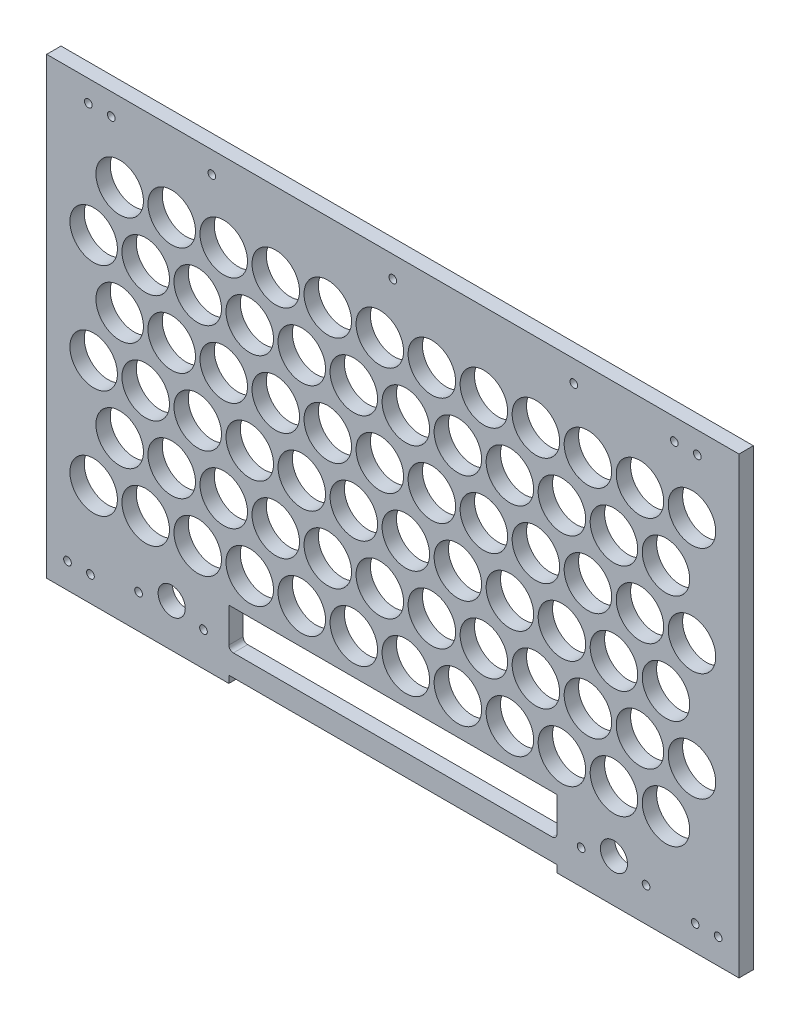
SolidWorks part; units mm, degrees
material "ABS"
ref_plane "X-Y Datum" through (0, 0, 0) normal (0, 0, 1) x (1, 0, 0)
ref_plane "X-Z Datum" through (0, 0, 0) normal (0, 1, 0) x (1, 0, 0)
ref_plane "Y-Z Datum" through (0, 0, 0) normal (1, 0, 0) x (0, 0, -1)
sketch "Sketch1" plane through (0, 0, 0) normal (0, 0, 1) x (1, 0, 0)
  line L1 (-143.025, 70.775) -> (143.025, 70.775)
  line L2 (-143.025, 70.775) -> (-143.025, -70.775)
  line L3 (-143.025, -70.775) -> (143.025, -70.775)
  line L4 (143.025, 70.775) -> (143.025, -70.775)
  line L5 (-143.025, 70.775) -> (143.025, -70.775) construction
  line L6 (-143.025, -70.775) -> (143.025, 70.775) construction
  line L13 (-153.025, -105.775) -> (153.025, -105.775)
  line L14 (-153.025, 91.65) -> (153.025, 91.65)
  line L15 (-153.025, 91.65) -> (-153.025, -105.775)
  line L16 (153.025, 91.65) -> (153.025, -105.775)
  line L17 (153.025, 70.775) -> (153.025, -70.775) construction
  line L18 (-143.025, 91.65) -> (143.025, 91.65) construction
  line L19 (-143.025, -105.775) -> (143.025, -105.775) construction
  line L20 (-153.025, 70.775) -> (-153.025, -70.775) construction
  line L21 (-132.25, -60) -> (-109.25, -60) construction
  circle A0 centre (-132.25, -60) radius 10.775
  circle A1 centre (-109.25, -60) radius 10.775 construction
  circle A2 centre (-120.75, -36) radius 10.775
  point P0 (0, 0)
  point P16 (-120.75, -60)
  dimension "D1" = 21.55
  dimension "D2" = 23
  dimension "D3" = 24
  dimension "D5" = 141.55
  dimension "D6" = 286.05
  dimension "D7" = 35
  dimension "D8" = 20.875
  dimension "D9" = 10
  dimension "D10" = 10
extrude "Boss-Extrude1" add sketch "Sketch1" along normal blind 6.35 contours A0 L3 L4 L1 L2 A2 | A2 | A0 | A0 L2 L3 | L1 L4 L3 L2 region at (2.4105, 0.9241, 0) region at (-140.6182, -68.3682, 0) region at (-132.25, -60, 0) region at (-149.383, -7.0625, 0) region at (-120.75, -36, 0)
sketch "Sketch3" plane through (0, 0, 6.35) normal (0, 0, 1) x (1, 0, 0)
  line L4 (143.025, 70.775) -> (-143.025, 70.775)
  line L5 (143.025, -70.775) -> (143.025, 70.775)
  line L6 (-143.025, -70.775) -> (143.025, -70.775)
  line L7 (-143.025, 70.775) -> (-143.025, -70.775)
  line L8 (143.025, 70.775) -> (-143.025, 70.775)
  line L9 (143.025, -70.775) -> (143.025, 70.775)
  line L10 (-143.025, -70.775) -> (143.025, -70.775)
  line L11 (-143.025, 70.775) -> (-143.025, -70.775)
  circle A0 centre (-132.25, -60) radius 10.4988
  circle A1 centre (-120.75, -36) radius 10.775
  circle A2 centre (-120.75, -36) radius 10.775 construction
  circle A3 centre (-132.25, -60) radius 10.775
  circle A4 centre (-132.25, -60) radius 10.775 construction
  circle A5 centre (-120.75, -36) radius 10.4988
  dimension "D4" = 20.9976
  dimension "D1" = 0
  dimension "D2" = 0
  dimension "D3" = 0
extrude "Cut-Extrude1" cut sketch "Sketch3" against normal through all contours A4 | A0 region at (-132.25, -60, 6.35)
sketch "Sketch4" plane through (0, 0, 6.35) normal (0, 0, 1) x (1, 0, 0)
  line L4 (143.025, 70.775) -> (-143.025, 70.775)
  line L5 (143.025, -70.775) -> (143.025, 70.775)
  line L6 (-143.025, -70.775) -> (143.025, -70.775)
  line L7 (-143.025, 70.775) -> (-143.025, -70.775)
  line L8 (143.025, 70.775) -> (-143.025, 70.775)
  line L9 (143.025, -70.775) -> (143.025, 70.775)
  line L10 (-143.025, -70.775) -> (143.025, -70.775)
  line L11 (-143.025, 70.775) -> (-143.025, -70.775)
  line L12 (143.025, 70.775) -> (-143.025, 70.775)
  line L13 (-143.025, 70.775) -> (-143.025, -70.775)
  line L14 (-143.025, -70.775) -> (143.025, -70.775)
  line L15 (143.025, -70.775) -> (143.025, 70.775)
  line L16 (143.025, 70.775) -> (-143.025, 70.775)
  line L17 (-143.025, 70.775) -> (-143.025, -70.775)
  line L18 (-143.025, -70.775) -> (143.025, -70.775)
  line L19 (143.025, -70.775) -> (143.025, 70.775)
  circle A1 centre (-120.75, -36) radius 10.4988
  circle A3 centre (-120.75, -36) radius 10.4988
  circle A5 centre (-132.25, -60) radius 10.4988
  circle A6 centre (-132.25, -60) radius 10.4988
  dimension "D4" = 0
  dimension "D1" = 0
  dimension "D2" = 0
  dimension "D3" = 0
extrude "Cut-Extrude2" cut sketch "Sketch4" against normal through all contours A3 region at (-120.75, -36, 6.35)
pattern_linear "LPattern1" count 12 spacing 23 along (1, 0, 0) of "Cut-Extrude1", "Cut-Extrude2"
pattern_linear "LPattern2" count 3 spacing 48 along (0, 1, 0) of "LPattern1"
sketch "Sketch5" plane through (0, 0, 0) normal (0, 0, -1) x (-1, 0, 0)
sketch "Sketch13" plane through (0, 91.65, 0) normal (0, 1, 0) x (1, 0, 0)
  line L4 (153.025, 0) -> (-153.025, 0)
  line L5 (-153.025, 0) -> (-153.025, -6.35)
  line L6 (-153.025, -6.35) -> (153.025, -6.35)
  line L7 (153.025, -6.35) -> (153.025, 0)
  line L8 (153.025, 0) -> (-153.025, 0)
  line L9 (-153.025, 0) -> (-153.025, -6.35)
  line L10 (-153.025, -6.35) -> (153.025, -6.35)
  line L11 (153.025, -6.35) -> (153.025, 0)
  dimension "D1" = 0
extrude "Boss-Extrude2" add sketch "Sketch13" along normal blind 3.175
sketch "Sketch14" plane through (0, 0, 0) normal (0, 0, -1) x (-1, 0, 0)
  circle A0 centre (-97.75, -86.775) radius 6
extrude "Cut-Extrude3" cut sketch "Sketch14" against normal through all
mirror "Mirror1" about plane through (0, 0, 0) normal (1, 0, 0) of "Cut-Extrude3"
sketch "Sketch15" plane through (0, 0, 0) normal (0, 0, -1) x (-1, 0, 0)
  point P0 (-111.94, -90.775)
  point P1 (-83.25, -90.775)
  point P3 (83.712, -90.775)
  point P11 (80, 85.3)
  point P13 (0, 85.3)
  point P15 (-80, 85.3)
  point P41 (112.402, -90.775)
  point P47 (-143.8175, -94.6)
  point P50 (-133.6575, -94.6)
  point P54 (-134.61, 85.3)
  point P57 (-124.45, 85.3)
  point P61 (124.45, 85.3)
  point P64 (134.61, 85.3)
  point P68 (133.6575, -94.6)
  point P71 (143.8175, -94.6)
hole_wizard "M3 Clearance Hole1" positions "Sketch15" profile "Sketch16" hole size "M3" standard "ANSI Metric" end condition through all
sketch "Sketch16" plane through (111.94, -90.775, 0) normal (1, 0, 0) x (0, 1, 0)
  line L0 (0, 0) -> (0, 6.35)
  line L1 (0, 6.35) -> (1.7, 6.35)
  line L2 (1.7, 6.35) -> (1.7, 0)
  line L5 (1.7, 0) -> (0, 0)
  line L11 (0, -6.35) -> (0, 107.95) construction
  dimension "Thru Hole Dia." = 3.4
  dimension "Thru Hole Depth" = 6.35
sketch "Sketch17" plane through (0, 0, 0) normal (0, 0, -1) x (-1, 0, 0)
  line L0 (0, -105.775) -> (0, -77.9164) construction
  line L1 (153.025, -105.775) -> (-153.025, -105.775) construction
  circle A0 centre (0, -90.775) radius 2.25
  circle A1 centre (140.5494, 12) radius 2.25
  circle A2 centre (-140.6875, -12) radius 2.25
  point P0 (-140.6875, -12)
  point P1 (140.5494, 12)
  point P9 (0, -90.775)
  point P11 (83.712, -90.775)
  dimension "D1" = 4.5
extrude "Cut-Extrude4" [suppressed] cut sketch "Sketch17" against normal through all
sketch "Sketch18" plane through (0, -105.775, 0) normal (0, -1, 0) x (1, 0, 0)
  line L0 (0, 0) -> (0, 6.35)
  line L1 (-153.025, 0) -> (153.025, 0) construction
  line L2 (-153.025, 6.35) -> (153.025, 6.35) construction
  line L4 (-72.5, 6.35) -> (72.5, 6.35)
  line L5 (-72.5, 6.35) -> (-72.5, 0)
  line L6 (-72.5, 0) -> (72.5, 0)
  line L7 (72.5, 6.35) -> (72.5, 0)
  line L8 (-72.5, 6.35) -> (72.5, 0) construction
  line L9 (-72.5, 0) -> (72.5, 6.35) construction
  point P6 (0, 3.175)
  line M3 (-153.025, 0) -> (153.025, 0)
  line M5 (153.025, 6.35) -> (-153.025, 6.35)
  dimension "D1" = 145
extrude "Cut-Extrude5" cut sketch "Sketch18" against normal blind 30 contours L7 L0 M5 M3 | L5 L0 M5 M3 region at (-36.25, -105.775, 3.175) region at (36.25, -105.775, 3.175)
fillet "Fillet1" [suppressed] radius 8
sketch "Sketch19" plane through (0, 0, 0) normal (0, 0, -1) x (-1, 0, 0)
  line L0 (-72.5, -75.775) -> (-72.5, -105.775) construction
  line L1 (-72.5, -102.6) -> (72.5, -102.6)
  line L2 (-72.5, -102.6) -> (-72.5, -93.075)
  line L3 (-72.5, -93.075) -> (72.5, -93.075)
  line L4 (72.5, -102.6) -> (72.5, -93.075)
  line L5 (72.5, -75.775) -> (72.5, -105.775) construction
  line L6 (-72.5, -105.775) -> (-153.025, -105.775) construction
  dimension "D1" = 3.175
  dimension "D2" = 9.525
extrude "Boss-Extrude3" add sketch "Sketch19" against normal blind 6.35
fillet "Fillet2" radius 2 2 edges at (72.5, -93.075, 3.175) (-72.5, -93.075, 3.175)
